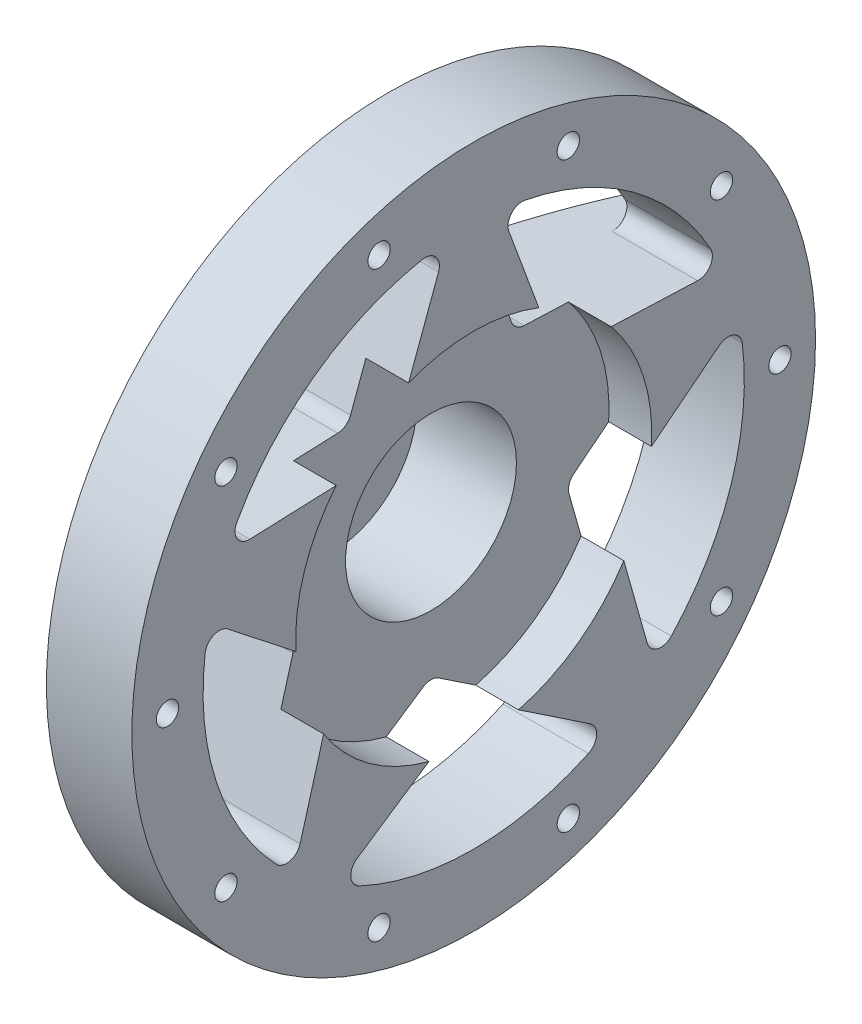
SolidWorks part; units mm, degrees
material "6061-T6 (SS)"
ref_plane "Front Plane" through (0, 0, 0) normal (0, 0, 1) x (1, 0, 0)
ref_plane "Top Plane" through (0, 0, 0) normal (0, 1, 0) x (1, 0, 0)
ref_plane "Right Plane" through (0, 0, 0) normal (1, 0, 0) x (0, 0, -1)
sketch "Sketch1" plane through (0, 0, 0) normal (0, 0, 1) x (1, 0, 0)
  line L0 (0, 0) -> (-29.1503, 0) construction
  line L1 (0, 19.05) -> (0, 76.2)
  line L2 (0, 76.2) -> (-19.05, 76.2)
  line L3 (0, 19.05) -> (-36.9755, 19.05)
  line L4 (-38.1, 0) -> (-31.75, 0)
  line L5 (-31.75, 0) -> (-31.75, 19.05)
  line L6 (-38.1, 0) -> (-38.1, -5.1888)
  arc A0 (-19.05, 76.2) -> (-36.9755, 19.05) centre (123.825, 0) ccw
  arc A1 (-36.9755, 19.05) -> (-38.1, 0) centre (123.825, 0) ccw
  dimension "D5" = 31.75
  dimension "D1" = 38.1
  dimension "D2" = 38.1
  dimension "D3" = 152.4
  dimension "D4" = 19.05
revolve "Revolve1" add sketch "Sketch1" angle 360 about L0 region at (-15.4366, 44.7981, 0) region at (-34.7472, 9.2265, 0)
sketch "Sketch3" plane through (0, 0, 0) normal (1, 0, 0) x (0, 0, -1)
  line L0 (44.7676, -61.6628) -> (0, -31.75)
  line L1 (0, -31.75) -> (-44.7676, -61.6628)
  line L2 (0, -31.75) -> (0, 0) construction
  line L3 (44.7676, -61.6628) -> (-44.7676, -61.6628) construction
  circle A0 centre (0, 0) radius 76.2 construction
  arc A1 (44.7676, -61.6628) -> (-44.7676, -61.6628) centre (0, 0) cw
  dimension "D1" = 112.5
  dimension "D2" = 31.75
extrude "Cut-Extrude2" cut sketch "Sketch3" against normal through all from offset 19.05 offset against normal yes
fillet "Fillet1" radius 3.175 1 edges at (-27.0034, -31.75, 0)
pattern_circular "CirPattern1" count 5 over 360 about axis through (0, 0, 0) along (1, 0, 0) of "Fillet1", "Cut-Extrude2"
sketch "Sketch4" plane through (-19.05, 0, 0) normal (-1, 0, 0) x (0, 0, 1)
  line L0 (-1.7639, -32.9286) -> (-30.434, -52.0853)
  line L1 (-44.7676, -61.6628) -> (-1.7639, -32.9286) construction
  line L2 (1.7639, -32.9286) -> (44.7676, -61.6628) construction
  line L3 (30.434, -52.0853) -> (1.7639, -32.9286)
  arc A0 (-30.434, -52.0853) -> (30.434, -52.0853) centre (0, 0) ccw
  arc A1 (-1.7639, -32.9286) -> (1.7639, -32.9286) centre (0, -35.5685) cw
  dimension "D1" = 60.325
extrude "Cut-Extrude3" cut sketch "Sketch4" against normal through all
fillet "Fillet2" radius 3.175 2 edges at (-9.525, -52.0853, 30.434) (-9.525, -52.0853, -30.434)
pattern_circular "CirPattern2" count 5 over 360 about axis through (0, 0, 0) along (1, 0, 0) of "Fillet2", "Cut-Extrude3"
sketch "Sketch5" plane through (-19.05, 0, 0) normal (-1, 0, 0) x (0, 0, 1)
  line L0 (0, 0) -> (-21.0943, -64.9215)
  line L1 (-21.0943, -64.9215) -> (21.0943, -64.9215)
  line L2 (21.0943, -64.9215) -> (0, 0)
  circle A3 centre (-21.0943, -64.9215) radius 2.4892
  circle A4 centre (21.0943, -64.9215) radius 2.4892
  point P3 (0, -64.9215)
  dimension "D2" = 68.2625
  dimension "D3" = 4.9784
  dimension "D1" = 36
extrude "Cut-Extrude4" cut sketch "Sketch5" against normal through all contours A3 | A4
pattern_circular "CirPattern3" count 5 over 360 about axis through (-19.05, 0, 0) along (1, 0, 0) of "Cut-Extrude4"
sketch "Sketch6" plane through (0, 0, 0) normal (1, 0, 0) x (0, 0, -1)
  circle A0 centre (0, 0) radius 39.6875
  circle M43 centre (0, 0) radius 19.05
  dimension "D1" = 79.375
extrude "Cut-Extrude6" cut sketch "Sketch6" against normal blind 9.525 contours A0 M43 region at (0, 0, 38.565)
